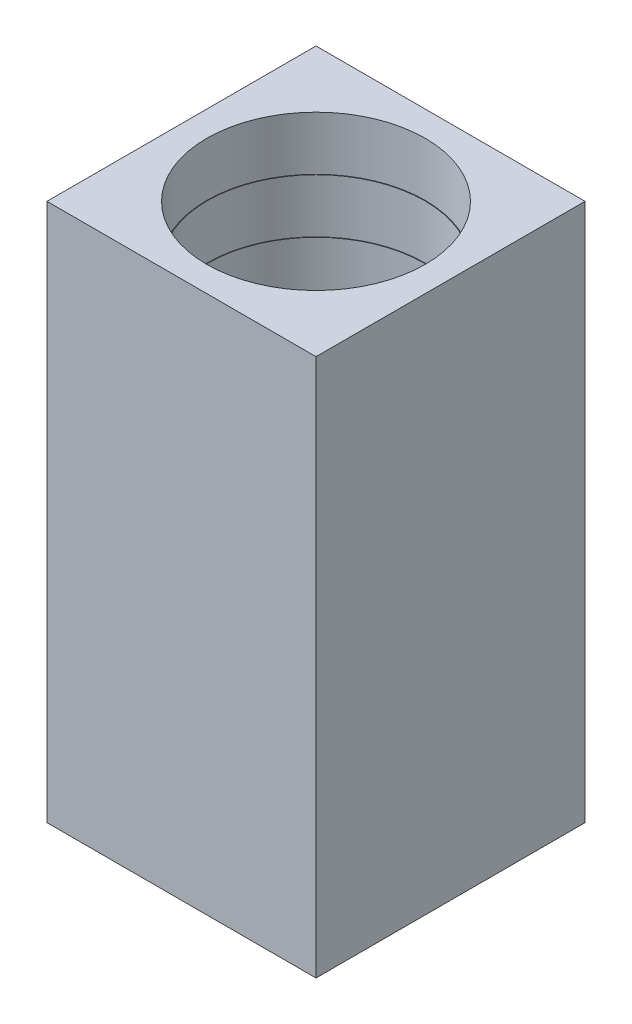
SolidWorks part; units mm, degrees
ref_plane "Front Plane" through (0, 0, 0) normal (0, 0, 1) x (1, 0, 0)
ref_plane "Top Plane" through (0, 0, 0) normal (0, 1, 0) x (1, 0, 0)
ref_plane "Right Plane" through (0, 0, 0) normal (1, 0, 0) x (0, 0, -1)
sketch "Sketch1" plane through (0, 0, 0) normal (0, 1, 0) x (1, 0, 0)
  line L1 (-25, 25) -> (25, 25)
  line L2 (-25, 25) -> (-25, -25)
  line L3 (-25, -25) -> (25, -25)
  line L4 (25, 25) -> (25, -25)
  line L5 (-25, 25) -> (25, -25) construction
  line L6 (-25, -25) -> (25, 25) construction
  point P0 (0, 0)
  dimension "D1" = 50
  dimension "D2" = 50
extrude "Boss-Extrude1" add sketch "Sketch1" along normal blind 100
sketch "Sketch2" plane through (0, 100, 0) normal (0, 1, 0) x (1, 0, 0)
  circle A12 centre (0, 0) radius 20
  circle A25 centre (0, 0) radius 19.9
  circle A26 centre (0, 0) radius 20.1
  circle A27 centre (0, 0) radius 20.2
  circle A28 centre (0, 0) radius 20.3
  point P0 (0, 0)
  point P10 (0, 0)
  point P11 (0, 0)
  point P12 (0, 0)
  point P13 (0, 0)
  dimension "D5" = 40
  dimension "D22" = 0.1
  dimension "D23" = 0.1
  dimension "D24" = 0.1
  dimension "D25" = 0.1
extrude "Cut-Extrude2" cut sketch "Sketch2" against normal blind 50 contours A25 region at (0, 100, 0)
extrude "Cut-Extrude3" cut sketch "Sketch2<5>" against normal blind 40 contours A12 A25 region at (-19.9434, 100, 0)
sketch "Sketch2<5>" plane through (0, 100, 0) normal (0, 1, 0) x (1, 0, 0) same geometry as "Sketch2"
extrude "Cut-Extrude4" cut sketch "Sketch2<6>" against normal blind 30 contours A26 A12 region at (-20.0431, 100, 0)
sketch "Sketch2<6>" plane through (0, 100, 0) normal (0, 1, 0) x (1, 0, 0) same geometry as "Sketch2"
extrude "Cut-Extrude5" cut sketch "Sketch2<7>" against normal blind 20 contours A27 A26 region at (-20.1429, 100, 0)
sketch "Sketch2<7>" plane through (0, 100, 0) normal (0, 1, 0) x (1, 0, 0) same geometry as "Sketch2"
extrude "Cut-Extrude6" cut sketch "Sketch2<8>" against normal blind 10 contours A28 A27 region at (-20.2426, 100, 0)
sketch "Sketch2<8>" plane through (0, 100, 0) normal (0, 1, 0) x (1, 0, 0) same geometry as "Sketch2"
